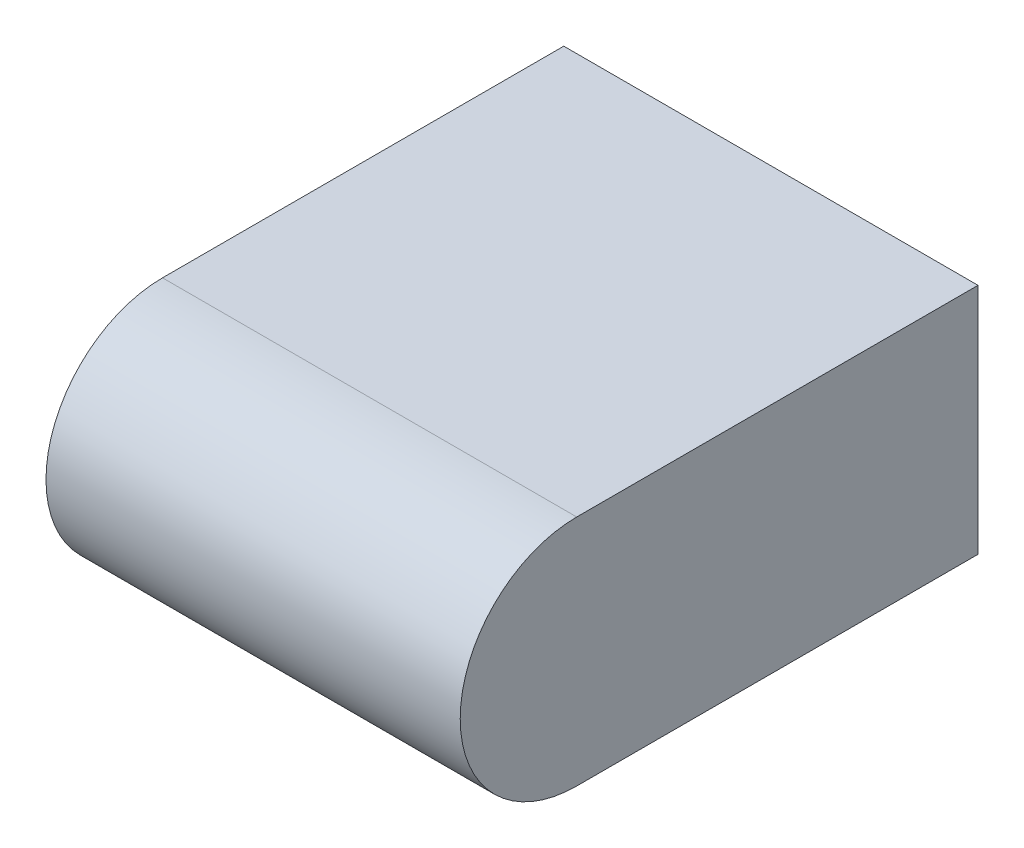
SolidWorks part; units mm, degrees
ref_plane "Ön Düzlem" through (0, 0, 0) normal (0, 0, 1) x (1, 0, 0)
ref_plane "Üst Düzlem" through (0, 0, 0) normal (0, 1, 0) x (1, 0, 0)
ref_plane "Sağ Düzlem" through (0, 0, 0) normal (1, 0, 0) x (0, 0, -1)
sketch "Çizim1" plane through (0, 0, 0) normal (0, 1, 0) x (1, 0, 0)
  line L1 (-16, -20) -> (16, -20)
  line L2 (-16, -20) -> (-16, 20)
  line L3 (-16, 20) -> (16, 20)
  line L4 (16, -20) -> (16, 20)
  line L5 (-16, -20) -> (16, 20) construction
  line L6 (-16, 20) -> (16, -20) construction
  point P0 (0, 0)
  dimension "D1" = 40
  dimension "D2" = 32
extrude "Yükseklik-Ekstrüzyon1" add sketch "Çizim1" along normal blind 18
fillet "Radyus1" 2 edges at (0, 18, 20) (0, 0, 20) type full round first side face at (0, 18, 0) second side face at (0, 0, 0) middle face at (0, 9, 20)
